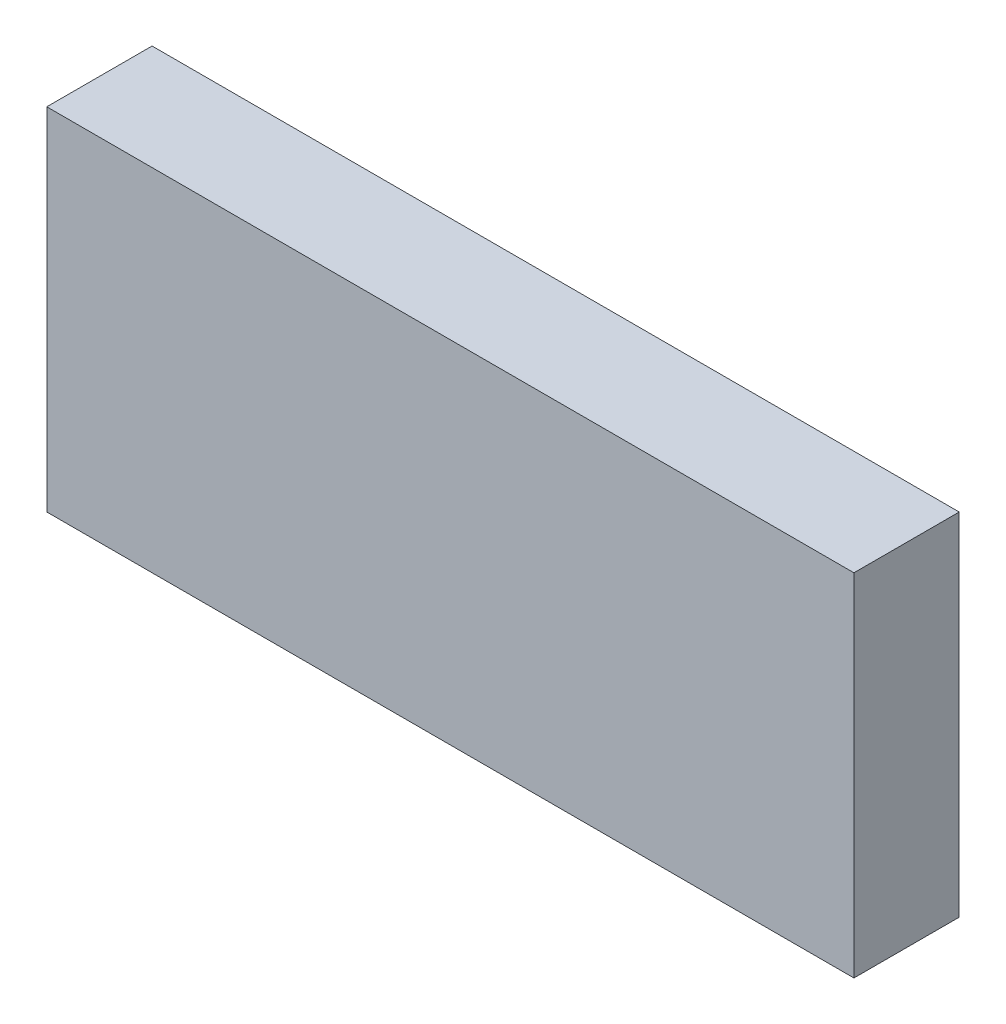
SolidWorks part; units mm, degrees
ref_plane "Front Plane" through (0, 0, 0) normal (0, 0, 1) x (1, 0, 0)
ref_plane "Top Plane" through (0, 0, 0) normal (0, 1, 0) x (1, 0, 0)
ref_plane "Right Plane" through (0, 0, 0) normal (1, 0, 0) x (0, 0, -1)
sketch "Sketch2" plane through (0, 0, 0) normal (0, 0, 1) x (1, 0, 0)
  line L1 (23, 10) -> (-23, 10)
  line L2 (23, 10) -> (23, -10)
  line L3 (23, -10) -> (-23, -10)
  line L4 (-23, 10) -> (-23, -10)
  line L5 (23, 10) -> (-23, -10) construction
  line L6 (23, -10) -> (-23, 10) construction
  ellipse E0 centre (0, 0) end of major axis (23, 0) minor radius 10 construction
  point P1 (0, 0)
  dimension "D1" = 10
  dimension "D2" = 23
extrude "Boss-Extrude1" add sketch "Sketch2" along normal blind 6
